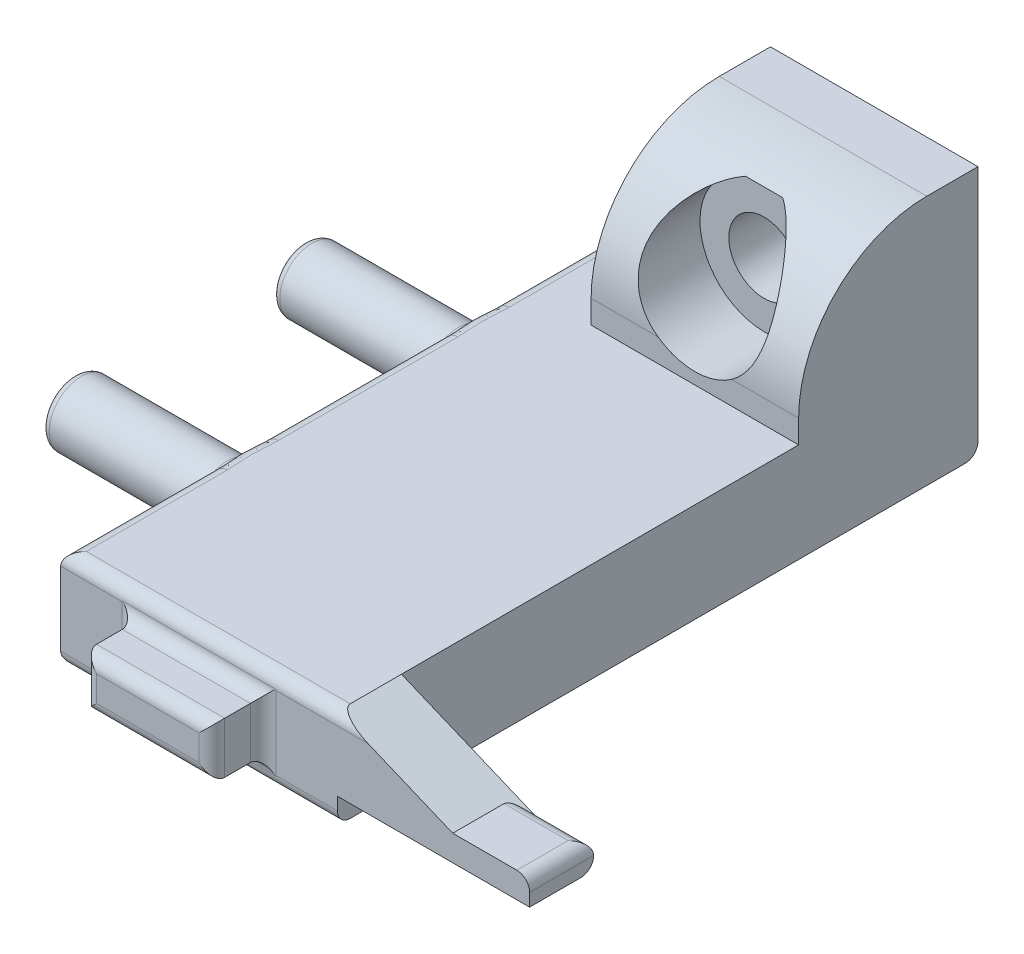
SolidWorks part; units mm, degrees
ref_plane "Plan de face" through (0, 0, 0) normal (0, 0, 1) x (1, 0, 0)
ref_plane "Plan de dessus" through (0, 0, 0) normal (0, 1, 0) x (1, 0, 0)
ref_plane "Plan de droite" through (0, 0, 0) normal (1, 0, 0) x (0, 0, -1)
sketch "Esquisse1" plane through (0, 0, 0) normal (0, 1, 0) x (1, 0, 0)
  line L1 (10.8, -25) -> (-10.8, -25)
  line L2 (10.8, -25) -> (10.8, 25)
  line L3 (10.8, 25) -> (-10.8, 25)
  line L4 (-10.8, -25) -> (-10.8, 25)
  line L5 (10.8, -25) -> (-10.8, 25) construction
  line L6 (10.8, 25) -> (-10.8, -25) construction
  point P0 (0, 0)
  dimension "D1" = 21.6
  dimension "D2" = 50
extrude "Boss.-Extru.1" add sketch "Esquisse1" along normal mid plane 7.75
sketch "Esquisse2" plane through (10.8, 0, 0) normal (1, 0, 0) x (0, 0, -1)
  line L0 (25, 3.875) -> (25, 15.685)
  line L1 (25, 15.685) -> (21, 15.685)
  line L2 (11, 5.685) -> (11, 3.875)
  line L3 (-25, 3.875) -> (11, 3.875) construction
  line L4 (11, 3.875) -> (25, 3.875)
  arc A0 (21, 15.685) -> (11, 5.685) centre (21, 5.685) ccw
  dimension "D3" = 10
  dimension "D1" = 14
  dimension "D2" = 11.81
extrude "Boss.-Extru.2" add sketch "Esquisse2" against normal blind 16.2
sketch "Esquisse3" plane through (0, 0, -25) normal (0, 0, -1) x (-1, 0, 0)
  line L15 (10.8, 3.875) -> (10.8, -3.875) construction
  line L16 (5.4, 3.875) -> (10.8, 3.875) construction
  circle A2 centre (1.55, 9.7795) radius 1.125
  circle A3 centre (-2.7, 9.7795) radius 3
  dimension "D1" = 6
  dimension "D2" = 2.25
  dimension "D3" = 9.25
  dimension "D4" = 13.5
  dimension "D5" = 5.9045
sketch "Esquisse8" plane through (0, 0, -11) normal (0, 0, 1) x (1, 0, 0)
  point P0 (2.7, 9.7795)
hole_wizard "Chambrage pour vis à six pans creux M51" positions "Esquisse8" profile "Esquisse6" counterbore size "M5" standard "ISO" end condition up to next
sketch "Esquisse6" plane through (2.7, 9.7795, -11) normal (1, 0, 0) x (0, -1, 0)
  line L0 (0, 0) -> (0, 14)
  line L1 (0, 14) -> (2.75, 14)
  line L3 (2.75, 14) -> (2.75, 5.4)
  line L4 (2.75, 5.4) -> (5, 5.4)
  line L5 (5, 5.4) -> (5, 0)
  line L7 (5, 0) -> (0, 0)
  line L11 (0, -6.35) -> (0, 107.95) construction
  dimension "Diamètre du perçage jusqu'au prochain" = 5.5
  dimension "Profondeur du perçage jusqu'au prochain" = 14
  dimension "Diamètre du chambrage" = 10
  dimension "Profondeur du chambrage" = 5.4
extrude "Enlèv. mat.-Extru.1" cut sketch "Esquisse3" against normal blind 4 contours A2
sketch "Esquisse9" plane through (-10.8, 0, 0) normal (-1, 0, 0) x (0, 0, 1)
  line L0 (-25, 3.875) -> (-25, -3.875) construction
  circle A0 centre (-7, 0) radius 2.5
  circle A1 centre (11, 0) radius 2.5
  dimension "D1" = 5
  dimension "D2" = 18
  dimension "D3" = 18
extrude "Boss.-Extru.3" add sketch "Esquisse9" along normal blind 13
sketch "Esquisse10" plane through (0, 0, 25) normal (0, 0, 1) x (1, 0, 0)
  line L1 (5, -2) -> (-5, -2)
  line L2 (5, -2) -> (5, 2)
  line L3 (5, 2) -> (-5, 2)
  line L4 (-5, -2) -> (-5, 2)
  line L5 (5, -2) -> (-5, 2) construction
  line L6 (5, 2) -> (-5, -2) construction
  point P0 (0, 0)
  dimension "D1" = 10
  dimension "D2" = 4
extrude "Boss.-Extru.4" add sketch "Esquisse10" along normal blind 4
sketch "Esquisse11" plane through (10.8, 0, 0) normal (1, 0, 0) x (0, 0, -1)
  line L1 (-25, 0.125) -> (-20, 0.125)
  line L2 (-25, 0.125) -> (-25, -1.875)
  line L3 (-25, -1.875) -> (-20, -1.875)
  line L4 (-20, 0.125) -> (-20, -1.875)
  line L6 (-25, 3.875) -> (-25, -3.875) construction
  line L7 (-25, -3.875) -> (25, -3.875) construction
  dimension "D1" = 5
  dimension "D2" = 2
  dimension "D3" = 2
extrude "Boss.-Extru.5" add sketch "Esquisse11" along normal blind 15
sketch "Esquisse12" plane through (0, 0, 20) normal (0, 0, -1) x (-1, 0, 0)
  line L5 (-10.8, 0.125) -> (-10.8, -3.875)
  line L8 (-10.8, 3.875) -> (-10.8, 0.125)
  line L9 (-10.8, -3.875) -> (-10.8, 0.125)
  line L10 (-10.8, 0.125) -> (-19.8, 0.125)
  line L11 (-10.8, 3.875) -> (-10.8, 0.125)
  line L12 (-25.8, 0.125) -> (-10.8, 0.125) construction
  line L13 (-19.8, 0.125) -> (-10.8, 3.875)
  line L14 (-25.8, -1.875) -> (-25.8, 0.125) construction
  dimension "D1" = 6
extrude "Boss.-Extru.6" add sketch "Esquisse12" against normal up to surface (5 mm away) up to face at (9.15, -0.4375, 25)
fillet "Congé1" radius 0.6 2 edges at (-23.8, 0, 13.5) (-23.8, 0, -4.5)
fillet "Congé2" radius 1 2 edges at (-10.8, 0, 8.5) (-10.8, 0, -9.5)
fillet "Congé3" radius 1 10 edges at (0, -3.875, -25) (0, -3.875, 25) (0, 3.875, 25) (-10.8, -3.875, 0) (-10.8, 0, -25) (-10.8, 3.875, 0) (-8.1, 3.875, -25) (25.8, 0.125, 22.5) (22.8, 0.125, 20) (18.3, -1.875, 20)
fillet "Congé4" radius 1 8 edges at (0, 2, 29) (5, 0, 29) (0, -2, 29) (-5, 0, 29) (5, 0, 25) (0, 2, 25) (-5, 0, 25) (0, -2, 25)
